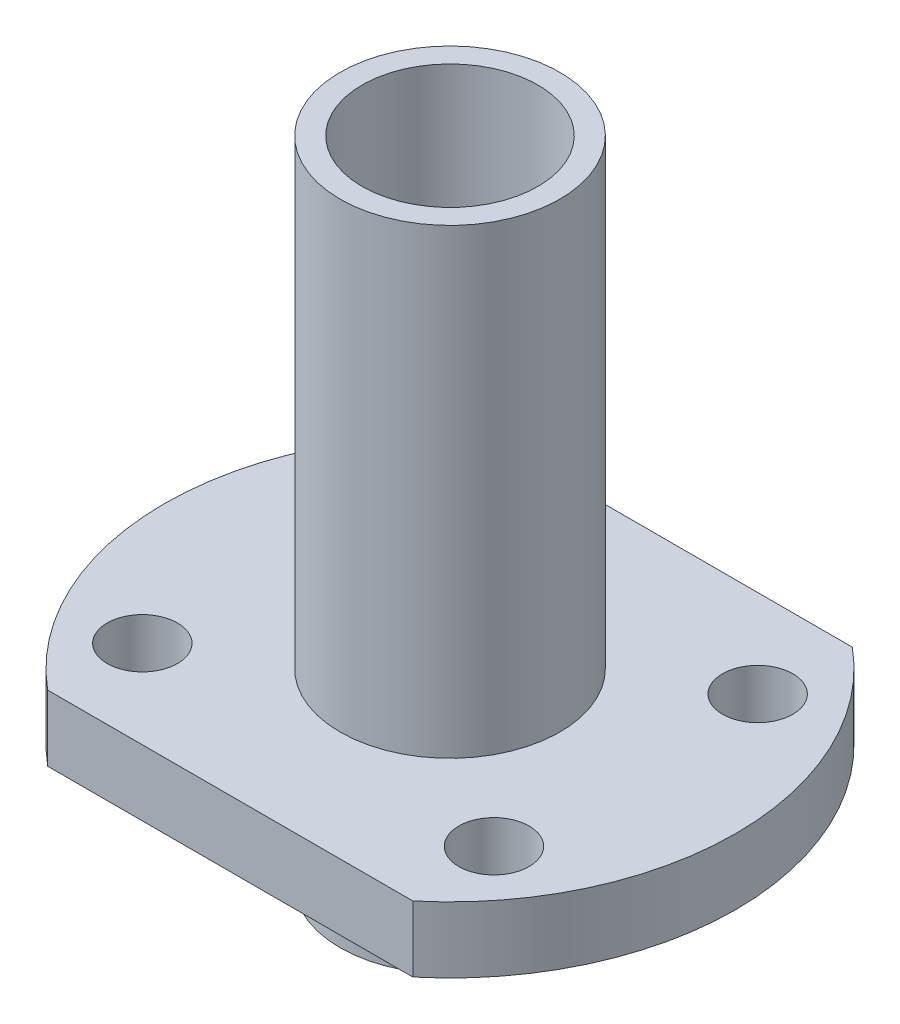
SolidWorks part; units mm, degrees
material "AISI 304"
ref_plane "Front Plane" through (0, 0, 0) normal (0, 0, 1) x (1, 0, 0)
ref_plane "Top Plane" through (0, 0, 0) normal (0, 1, 0) x (1, 0, 0)
ref_plane "Right Plane" through (0, 0, 0) normal (1, 0, 0) x (0, 0, -1)
sketch "Sketch1" plane through (0, 0, 0) normal (0, 1, 0) x (1, 0, 0)
  circle A0 centre (0, 0) radius 5
  dimension "D1" = 10
extrude "Boss-Extrude1" add sketch "Sketch1" along normal blind 29.5 contours A0
ref_plane "Plane1" through (0, 5.5, 0) normal (0, 1, 0) x (1, 0, 0)
sketch "Sketch2" plane through (0, 5.5, 0) normal (0, 1, 0) x (1, 0, 0)
  line L1 (-13, 10) -> (13, 10)
  line L2 (-13, 10) -> (-13, -10)
  line L3 (-13, -10) -> (13, -10)
  line L4 (13, 10) -> (13, -10)
  line L5 (-13, 10) -> (13, -10) construction
  line L6 (-13, -10) -> (13, 10) construction
  circle A0 centre (0, 0) radius 13
  dimension "D1" = 26
  dimension "D2" = 20
extrude "Boss-Extrude2" add sketch "Sketch2" along normal blind 3 contours L3 A0 L1 region at (0, 5.5, 0)
sketch "Sketch3" plane through (0, 29.5, 0) normal (0, 1, 0) x (1, 0, 0)
  circle A0 centre (0, 0) radius 4
  dimension "D1" = 8
extrude "Cut-Extrude1" cut sketch "Sketch3" against normal through all
sketch "Sketch4" plane through (0, 8.5, 0) normal (0, 1, 0) x (1, 0, 0)
  line L1 (8, -6) -> (-8, -6)
  line L2 (8, -6) -> (8, 6)
  line L3 (8, 6) -> (-8, 6)
  line L4 (-8, -6) -> (-8, 6)
  line L5 (8, -6) -> (-8, 6) construction
  line L6 (8, 6) -> (-8, -6) construction
  point P0 (0, 0)
  dimension "D1" = 12
  dimension "D2" = 16
hole_wizard "Ø3.2 (3.2) Diameter Hole1" positions "3DSketch1" profile "Sketch5" hole size "Ø3.2" standard "ISO" end condition through all
sketch3d "3DSketch1"
  point P0 (8, 8.5, 6)
  point P3 (8, 8.5, -6)
  point P6 (-8, 8.5, -6)
  point P9 (-8, 8.5, 6)
sketch "Sketch5" plane through (8, 8.5, 6) normal (1, 0, 0) x (0, 0, 1)
  line L0 (0, 0) -> (0, 8.5)
  line L1 (0, 8.5) -> (1.6, 8.5)
  line L2 (1.6, 8.5) -> (1.6, 0)
  line L5 (1.6, 0) -> (0, 0)
  line L11 (0, -6.35) -> (0, 107.95) construction
  dimension "Thru Hole Dia." = 3.2
  dimension "Thru Hole Depth" = 8.5
